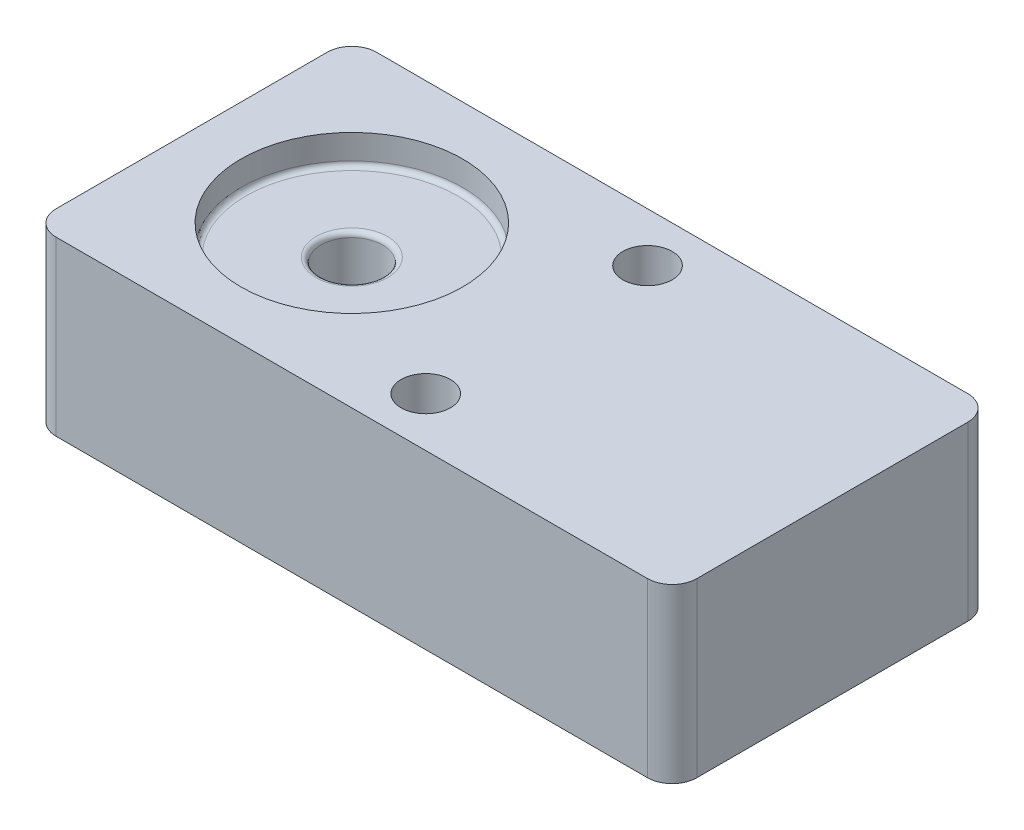
SolidWorks part; units mm, degrees
ref_plane "Plan de face" through (0, 0, 0) normal (0, 0, 1) x (1, 0, 0)
ref_plane "Plan de dessus" through (0, 0, 0) normal (0, 1, 0) x (1, 0, 0)
ref_plane "Plan de droite" through (0, 0, 0) normal (1, 0, 0) x (0, 0, -1)
sketch "Esquisse2" plane through (0, 0, 0) normal (0, 1, 0) x (1, 0, 0)
  line L1 (130, -65) -> (-130, -65)
  line L2 (130, -65) -> (130, 65)
  line L3 (130, 65) -> (-130, 65)
  line L4 (-130, -65) -> (-130, 65)
  line L5 (130, -65) -> (-130, 65) construction
  line L6 (130, 65) -> (-130, -65) construction
  point P0 (0, 0)
  dimension "D1" = 130
  dimension "D2" = 260
extrude "Boss.-Extru.2" add sketch "Esquisse2" along normal blind 70
sketch "Esquisse3" plane through (0, 70, 0) normal (0, 1, 0) x (1, 0, 0)
  line L0 (130, 65) -> (-130, 65) construction
  line L1 (-130, 65) -> (-130, -65) construction
  circle A0 centre (-65, 0) radius 45
  dimension "D1" = 65
  dimension "D2" = 90
  dimension "D3" = 65
extrude "Enlèv. mat.-Extru.1" cut sketch "Esquisse3" against normal blind 12
fillet "Congé1" radius 2 1 edges at (-65, 58, 45)
sketch "Esquisse4" plane through (0, 58, 0) normal (0, 1, 0) x (1, 0, 0)
  circle A0 centre (-65, 0) radius 12.5
extrude "Enlèv. mat.-Extru.2" cut sketch "Esquisse4" against normal blind 38
fillet "Congé2" radius 2 1 edges at (-65, 58, 12.5)
fillet "Congé3" radius 2 1 edges at (-65, 20, 12.5)
fillet "Congé4" radius 10 1 edges at (-130, 35, -65) type face fillet first side face at (0, 35, -65) second side face at (-130, 35, 0)
fillet "Congé5" radius 10 1 edges at (-130, 35, 65) type face fillet first side face at (-130, 35, 5) second side face at (0, 35, 65)
fillet "Congé6" radius 10 1 edges at (130, 35, 65) type face fillet first side face at (130, 35, 0) second side face at (5, 35, 65)
fillet "Congé7" radius 10 1 edges at (130, 35, -65) type face fillet first side face at (5, 35, -65) second side face at (130, 35, -5)
sketch "Esquisse6" plane through (0, 70, 0) normal (0, 1, 0) x (1, 0, 0)
  line L0 (-1000, 0) -> (49000, 0) construction
  line L1 (0, -1000) -> (0, 49000) construction
  line L2 (-1000, 45) -> (49000, 45) construction
  line L3 (10, -1000) -> (10, 49000) construction
  line L4 (120, 65) -> (-120, 65) construction
  circle A0 centre (10, 45) radius 10
  circle A1 centre (10, -45) radius 10
  dimension "D1" = 20
  dimension "D2" = 10
extrude "Enlèv. mat.-Extru.3" cut sketch "Esquisse6" against normal through all
